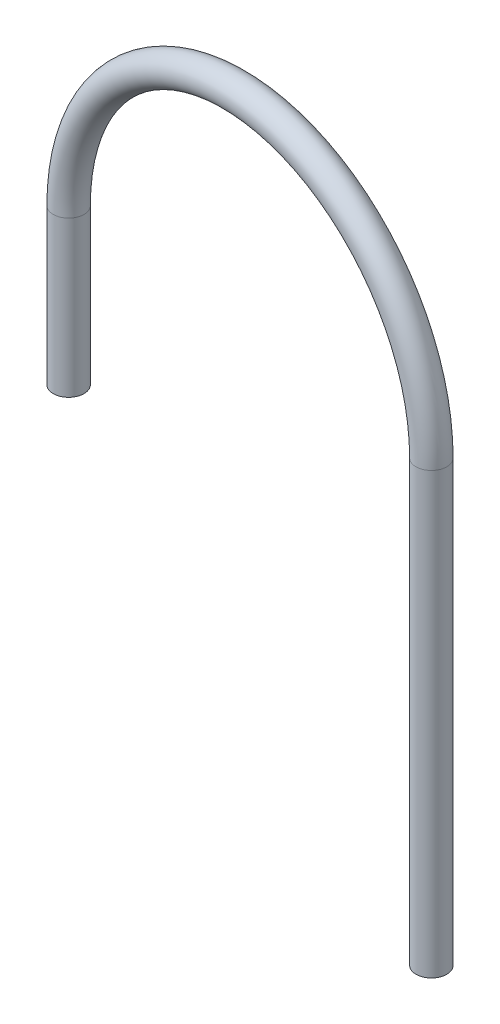
SolidWorks part; units mm, degrees
material "PE faible/moyenne densité"
ref_plane "Front" through (0, 0, 0) normal (0, 0, 1) x (1, 0, 0)
ref_plane "Top" through (0, 0, 0) normal (0, 1, 0) x (1, 0, 0)
ref_plane "Right" through (0, 0, 0) normal (1, 0, 0) x (0, 0, -1)
sketch3d "Esquisse3D1"
  line L0 (-42, 165, -59.25) -> (-42, 195.275, -59.25)
  line L1 (36, 195.275, -52) -> (36, 109.55, -52)
  arc A0 (-42, 195.275, -59.25) -> (36, 195.275, -52) centre (-3, 195.275, -55.625) ccw
  circle A1 centre (36, 117.55, -52) radius 1.1 construction
  point P3 (0.625, 195.275, -94.625)
  point P9 (36, 116.45, -52)
  dimension "D4" = 85.725
  dimension "D1" = 165
  dimension "D2" = 59.25
  dimension "D3" = 42
  dimension "D5" = 109.55
sweep "Balayage-Mince1" add path "Esquisse3D1" circular profile diameter 6 parameters "D1"=1, "D3"=6
equation "\"D4@Esquisse3D1\"=100-((\"D5@Esquisse3D1\"-81)/2)"
